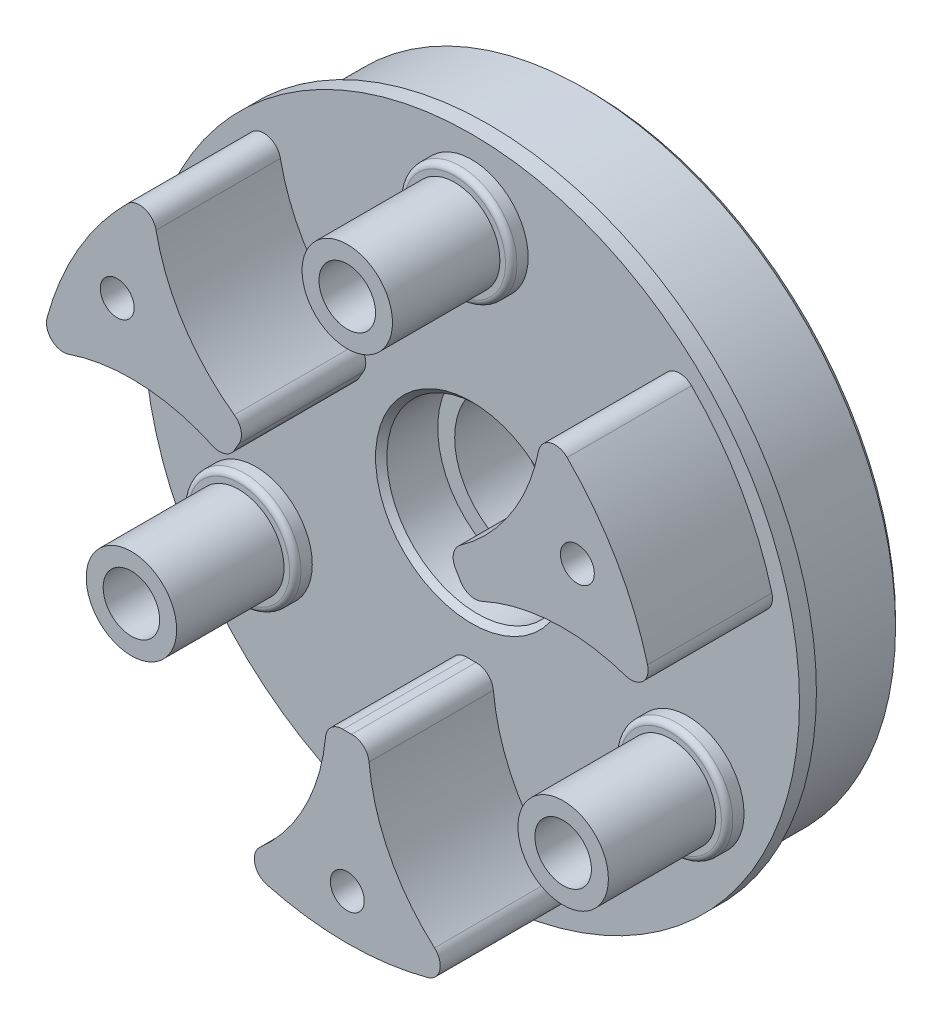
SolidWorks part; units mm, degrees
material "ABS"
ref_plane "Front Plane" through (0, 0, 0) normal (0, 0, 1) x (1, 0, 0)
ref_plane "Top Plane" through (0, 0, 0) normal (0, 1, 0) x (1, 0, 0)
ref_plane "Right Plane" through (0, 0, 0) normal (1, 0, 0) x (0, 0, -1)
sketch "Sketch1" plane through (0, 0, 0) normal (0, 0, 1) x (1, 0, 0)
  circle A0 centre (0, 0) radius 27.5
  circle A1 centre (0, 0) radius 22.05 construction
  circle A2 centre (0, 22.05) radius 2.5
  circle A3 centre (19.0959, -11.025) radius 2.5
  circle A78 centre (-19.0959, -11.025) radius 2.5
  point P15 (0, 0)
  dimension "D1" = 55
  dimension "D2" = 44.1
  dimension "D3" = 5
  dimension "D4" = 3
extrude "Boss-Extrude1" add sketch "Sketch1" along normal blind 10.5
sketch "Sketch2" plane through (0, 0, 10.5) normal (0, 0, 1) x (1, 0, 0)
  circle A0 centre (0, 22.05) radius 4
  circle A2 centre (0, 22.05) radius 2.5 construction
  circle A5 centre (0, 22.05) radius 2.5
  point P15 (0, 0)
  dimension "D1" = 8
extrude "Boss-Extrude2" add sketch "Sketch2" along normal blind 11
sketch "Sketch3" plane through (0, 0, 10.5) normal (0, 0, 1) x (1, 0, 0)
  arc A2 (5, 22.05) -> (5, 22.05) centre (0, 22.05) ccw
  circle A3 centre (0, 22.05) radius 5
  circle M5 centre (0, 22.05) radius 4
extrude "Boss-Extrude3" add sketch "Sketch3" along normal blind 1.5 contours A3 M5
sketch "Sketch4" plane through (0, 0, 10.5) normal (0, 0, 1) x (1, 0, 0)
  line L0 (0, 0) -> (-23.8157, 13.75) construction
  line L1 (0, 0) -> (0, 22.05) construction
  circle A0 centre (0, 0) radius 27.5 construction
  circle A1 centre (0, 0) radius 27.5
  circle A2 centre (0, 22.05) radius 15.75 construction
  circle A6 centre (0, 0) radius 22.05 construction
  arc A8 (-17.2387, 21.4261) -> (-8.7314, 7.173) centre (0, 22.05) ccw
  circle A9 centre (0, 0) radius 11.3
  circle A11 centre (0, 0) radius 6.3 construction
  arc A13 (-27.1749, 4.2161) -> (-10.5777, 3.9751) centre (-19.0959, -11.025) cw
  circle A16 centre (0, 22.05) radius 17.25 construction
  point P15 (0, 0)
  point P25 (0, 0)
  dimension "D1" = 31.5
  dimension "D5" = 12.6
  dimension "D4" = 5
  dimension "D2" = 60
  dimension "D3" = 1.5
extrude "Boss-Extrude4" add sketch "Sketch4" along normal blind 11 contours A1 A13 A9 A8
fillet "Fillet2" radius 0.5 1 edges at (5, 22.05, 12)
fillet "Fillet5" radius 1.5 4 edges at (-17.2387, 21.4261, 16) (-10.5777, 3.9751, 16) (-27.1749, 4.2161, 16) (-8.7314, 7.173, 16)
pattern_circular "CirPattern1" count 3 over 360 about axis through (0, 0, 0) along (0, 0, 1) of "Fillet2", "Boss-Extrude4", "Boss-Extrude3", "Boss-Extrude2", "Fillet5"
ref_plane "Plane1" through (0, 0, 21.5) normal (0, 0, 1) x (1, 0, 0)
sketch "Sketch5" plane through (0, 0, 21.5) normal (0, 0, 1) x (1, 0, 0)
  line L0 (0, 0) -> (-23.8157, 13.75) construction
  line L1 (0, 0) -> (0, 27.5) construction
  circle A0 centre (0, 0) radius 27.5 construction
  circle A3 centre (-20.3516, 11.75) radius 1.5
  circle A4 centre (0, 0) radius 27.5 construction
  arc A5 (-19.4485, 19.4424) -> (-26.5618, 7.1217) centre (0, 0) ccw construction
  dimension "D2" = 3
  dimension "D1" = 4
  dimension "D3" = 60
extrude "Cut-Extrude1" cut sketch "Sketch5" against normal through all
sketch "Sketch6" plane through (0, 0, 0) normal (0, 0, -1) x (-1, 0, 0)
  circle A0 centre (20.3516, 11.75) radius 2.75
  dimension "D1" = 5.5
extrude "Cut-Extrude2" cut sketch "Sketch6" against normal blind 3
sketch "Sketch7" plane through (0, 0, 0) normal (0, 0, -1) x (-1, 0, 0)
  circle A0 centre (0, 22.05) radius 4.25
  circle A1 centre (0, 0) radius 22.05 construction
  point P15 (0, 0)
  dimension "D1" = 8.5
extrude "Cut-Extrude3" cut sketch "Sketch7" against normal blind 5
pattern_circular "CirPattern2" count 3 over 360 about axis through (0, 0, 0) along (0, 0, 1) of "Cut-Extrude3", "Cut-Extrude2", "Cut-Extrude1"
chamfer "Chamfer1" distance 0.5 angle 45 1 edges at (27.5, 0, 0)
sketch "Sketch9" plane through (0, 0, 10.5) normal (0, 0, 1) x (1, 0, 0)
  circle A0 centre (0, 0) radius 8
  dimension "D1" = 16
extrude "Cut-Extrude4" cut sketch "Sketch9" against normal through all
sketch "Sketch10" plane through (0, 0, 0) normal (0, 0, -1) x (-1, 0, 0)
  circle A0 centre (0, 0) radius 8 construction
  circle A1 centre (0, 0) radius 8
  circle A2 centre (0, 0) radius 6.5
  dimension "D1" = 1.5
extrude "Boss-Extrude7" add sketch "Sketch10" against normal blind 5.5
chamfer "Chamfer2" distance 0.5 angle 45 1 edges at (8, 0, 10.5)
sketch "Sketch11" plane through (0, 0, 10.5) normal (0, 0, 1) x (1, 0, 0)
  circle A0 centre (0, 0) radius 27.5
  circle A1 centre (0, 0) radius 29
  dimension "D1" = 1.5
  dimension "D2" = 55
extrude "Boss-Extrude8" add sketch "Sketch11" against normal blind 1.5
equation "\"Nr\"= 108"
equation "\"module\"= 0.7"
equation "\"pressure_angle\"= 20.0deg"
equation "\"h_a\"= 0.7"
equation "\"h_f\"= 0.875"
equation "\"clr_tip_root\"= 0.17500000000000004"
equation "\"dp_r\"= 75.6"
equation "\"db_r\"= 71.04076213141467"
equation "\"fw_r\"= 8.0"
equation "\"alpha_r\"= 0.8539582918412449"
equation "\"beta_r\"= 3.374583250349157"
equation "\"bearing_ID\"= 55"
equation "\"bearing_OD\"= 72"
equation "\"bearing_height\"= 9"
equation "\"clearance_planet\"= 1.5"
equation "\"case_dist\"= 6.5"
equation "\"Motor_case_OD_max\"= 111.3"
equation "\"case_mounting_PCD\"= 103.8"
equation "\"bearing mount thickness\"= 8"
equation "\"case_mounting_hole_dia\"= 3"
equation "\"output_mounting_PCD\"= 80"
equation "\"output_mounting_hole_dia\"= 4"
equation "\"clearance_case_mount_holes_shell_thickness\"= 1"
equation "\"motor_case_OD_base\"= 101.8"
equation "\"sec_carrier_thickness\"= 5"
equation "\"sun_coupler_hub_thickness\"= 4"
equation "\"clearance_sun_coupler_sec_carrier\"= 1.5"
equation "\"clearance_motor_and_case\"= 5"
equation "\"motor_OD\"= 86.8"
equation "\"Motor_case_thickness\"= 2.5"
equation "\"Motor_case_ID\"= 96.8"
equation "\"case_mounting_hole_shift\"= 1.0"
equation "\"output_mounting_nut_wrench_size\"= 7"
equation "\"output_mounting_nut_thickness\"= 3.2"
equation "\"case_mounting_hole_allen_socket_dia\"= 5.5"
equation "\"output_mounting_nut_depth\"= 3"
equation "\"case_mounting_bolt_depth\"= 4.5"
equation "\"Ns\"= 18"
equation "\"Np\"= 45"
equation "\"ring_radial_thickness\"= 5.0"
equation "\"ring_OD\"= 85.6"
equation "\"ring_to_chamfer_clearance\"= 2"
equation "\"Motor_case_OD_base_to_chamfer\"= 5"
equation "\"pattern_offset_from_motor_case_OD_base\"= 3"
equation "\"pattern_bulge_dia\"= 3"
equation "\"pattern_num_bulge\"= 18"
equation "\"pattern_depth\"= 2"
equation "\"motor_height\"= 26.5"
equation "\"case_mounting_wrench_size\"= 5.5"
equation "\"case_mounting_nut_clearance\"= 2"
equation "\"base_plate_thickness\"= 4"
equation "\"case_mounting_nut_thickness\"= 2.4"
equation "\"case_mounting_surface_height\"= 4"
equation "\"motor_mount_hole_PCD\"= 32"
equation "\"motor_mount_hole_dia\"= 4"
equation "\"motor_mount_hole_num\"= 4"
equation "\"central_hole_offset_from_motor_mount_PCD\"= 5"
equation "\"wire_slot_dist_from_center\"= 30"
equation "\"wire_slot_length\"= 10"
equation "\"wire_slot_radius\"= 4"
equation "\"driver_upper_holes_dist_from_center\"= 23"
equation "\"driver_lower_holes_dist_from_center\"= 15"
equation "\"driver_side_holes_dist_from_center\"= 20"
equation "\"driver_mount_holes_dia\"= 2.5"
equation "\"driver_mount_inserts_OD\"= 3.5"
equation "\"driver_mount_thickness\"= 1.5"
equation "\"driver_mount_height\"= 4"
equation "\"air_flow_hole_offset\"= 3"
equation "\"num_planet\"= 3"
equation "\"planet_pin_bolt_dia\"= 5"
equation "\"planet_pin_socket_head_dia\"= 8.5"
equation "\"carrier_PCD\"= 44.099999999999994"
equation "\"D1@Sketch1\"=\"bearing_ID\""
equation "\"D2@Sketch1\"=\"carrier_PCD\""
equation "\"D3@Sketch1\"=\"planet_pin_bolt_dia\""
equation "\"D4@Sketch1\"=\"num_planet\""
equation "\"D1@Boss-Extrude1\"=\"bearing_height\"+\"carrier_bearing_step_width\""
equation "\"D1@Boss-Extrude2\"=\"fw_p\" + \"clearance_planet\"*2"
equation "\"D1@Boss-Extrude3\"=\"clearance_planet\""
equation "\"D1@Sketch4\"=\"Np\"*\"module\""
equation "\"D3@Sketch4\"=\"clearance_planet\""
equation "\"D1@Boss-Extrude4\"=\"fw_p\"+ \"clearance_planet\" * 2"
equation "\"D1@Fillet2\"=\"clearance_planet\"/3"
equation "\"D1@CirPattern1\"=\"num_planet\""
equation "\"D1@CirPattern2\"=\"num_planet\""
equation "\"D1@Boss-Extrude7\"=\"bearing_height\"+ \"carrier_bearing_step_width\" - \"sun_shaft_bearing_width\""
equation "\"planet_shaft_dia\"= 8"
equation "\"D1@Sketch2\"=\"planet_shaft_dia\""
equation "\"fw_p\"= 8.0"
equation "\"planet_shaft_step_offset\"= 1"
equation "\"D1@Sketch3\"=\"planet_shaft_step_offset\""
equation "\"carrier_trapezoidal_support_sun_offset\"= 5"
equation "\"D4@Sketch4\"=\"carrier_trapezoidal_support_sun_offset\""
equation "\"carrier_trapezoidal_support_hole_PCD_offset_bearing_ID\"= 4"
equation "\"carrier_trapezoidal_support_hole_dia\"= 3"
equation "\"D2@Sketch5\"=\"carrier_trapezoidal_support_hole_dia\""
equation "\"D1@Cut-Extrude2\"=\"carrier_trapezoidal_support_hole_dia\""
equation "\"carrier_trapezoidal_support_hole_socket_head_dia\"= 5.5"
equation "\"D1@Sketch6\"=\"carrier_trapezoidal_support_hole_socket_head_dia\""
equation "\"D1@Cut-Extrude3\"=\"planet_pin_bolt_dia\""
equation "\"D1@Sketch7\"=\"planet_pin_socket_head_dia\""
equation "\"carrier_bearing_step_width\"= 1.5"
equation "\"standard_clearance_1_5mm\"= 1.5"
equation "\"standard_fillet_1_5mm\"= 1.5"
equation "\"sun_shaft_bearing_OD\"= 16"
equation "\"D1@Sketch9\"=\"sun_shaft_bearing_OD\""
equation "\"D1@Sketch10\"=\"standard_clearance_1_5mm\""
equation "\"sun_shaft_bearing_width\"= 5"
equation "\"standard_bearing_insertion_chamfer\"= 0.5"
equation "\"D1@Chamfer1\"=\"standard_bearing_insertion_chamfer\""
equation "\"D1@Chamfer2\"=\"standard_bearing_insertion_chamfer\""
equation "\"D5@Sketch4\"=\"Ns\"*\"module\""
equation "\"D1@Sketch5\"=\"carrier_trapezoidal_support_hole_PCD_offset_bearing_ID\""
equation "\"D1@Plane1\"=\"fw_p\"+\"clearance_planet\"*2"
equation "\"D1@Sketch11\"=\"standard_clearance_1_5mm\""
equation "\"D2@Sketch11\"=\"bearing_ID\""
equation "\"D1@Boss-Extrude8\"=\"carrier_bearing_step_width\""
equation "\"D2@Sketch4\"=180/\"num_planet\""
equation "\"D3@Sketch5\"=180/\"num_planet\""
equation "\"D7@Sketch2\"=\"carrier_trapezoidal_support_hole_dia\""
equation "\"D5@Sketch2\"= 360 / ( 4 * \"Ns\" ) - \"alpha_s\""
equation "\"D3@Sketch2\"=\"dp_s\"- 2*\"h_b\""
equation "\"D9@Sketch2\"=\"carrier_trapezoidal_support_sun_offset\""
equation "\"carrier_trapezoidal_support_hole_wrench_size\"= 5.5"
equation "\"planet_pin_bolt_wrench_size\"= 8"
equation "\"pressure angle\"= 20.0deg"
equation "\"motor_output_hole_PCD\"= 23"
equation "\"motor_output_hole_dia\"= 4"
equation "\"motor_output_hole_num\"= 4"
equation "\"h_b\"= 0.875"
equation "\"dp_s\"= 12.6"
equation "\"db_s\"= 11.840127021902445"
equation "\"fw_s_calc\"= 6.9645987548691926"
equation "\"alpha_s\"= 0.8539582918412556"
equation "\"beta_s\"= 8.292083416317489"
equation "\"dp_p\"= 31.499999999999996"
equation "\"db_p\"= 29.600317554756113"
equation "\"alpha_p\"= 0.8539582918412343"
equation "\"beta_p\"= 2.2920834163175314"
equation "\"planet_bearing_OD\"= 12"
equation "\"planet_bearing_width\"= 3.5"
equation "\"planet_bore\"= 10"
equation "\"sun_shaft_bearing_ID\"= 8"
equation "\"sun_hub_dia\"= 33.0"
equation "\"sun_central_bolt_dia\"= 5"
equation "\"sun_central_bolt_socket_head_dia\"= 8.5"
equation "\"fw_s_used\"= 16.0"
equation "\"motor_output_hole_CSK_OD\"= 8"
equation "\"motor_output_hole_CSK_head_height\"= 2.0"
equation "\"bearing_retainer_thickness\"= 2"
